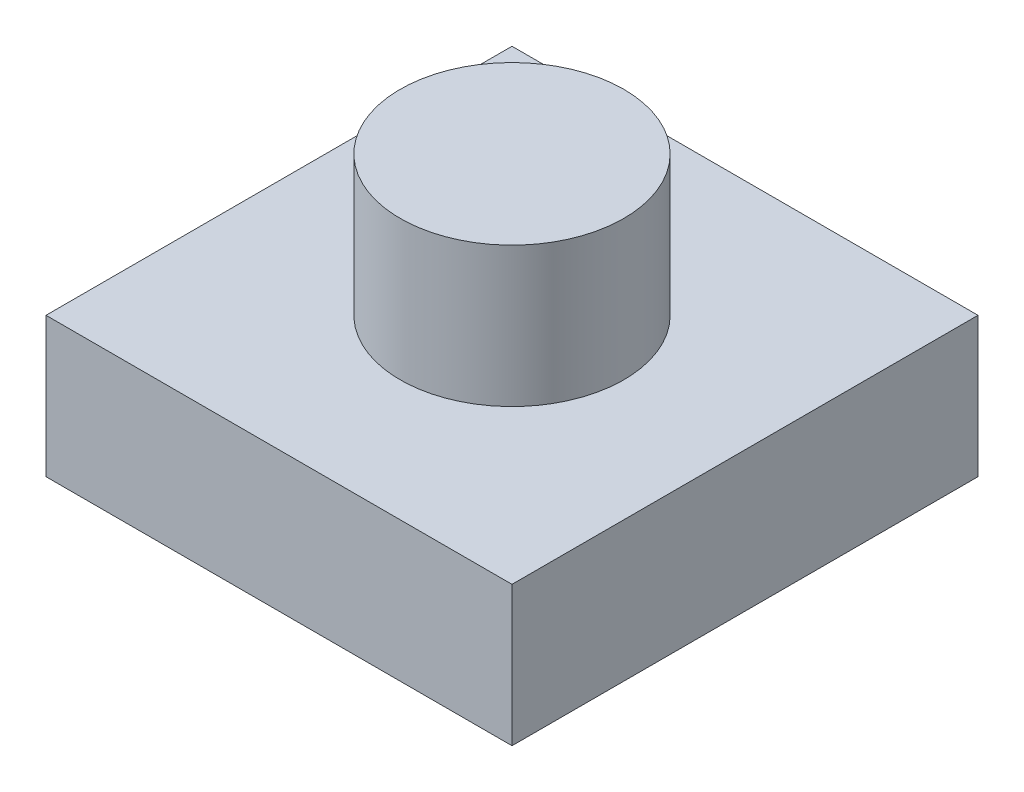
SolidWorks part; units mm, degrees
ref_plane "Front Plane" through (0, 0, 0) normal (0, 0, 1) x (1, 0, 0)
ref_plane "Top Plane" through (0, 0, 0) normal (0, 1, 0) x (1, 0, 0)
ref_plane "Right Plane" through (0, 0, 0) normal (1, 0, 0) x (0, 0, -1)
sketch "Sketch1" plane through (0, 0, 0) normal (0, 1, 0) x (1, 0, 0)
  line L1 (-6.35, 6.35) -> (6.35, 6.35)
  line L2 (-6.35, 6.35) -> (-6.35, -6.35)
  line L3 (-6.35, -6.35) -> (6.35, -6.35)
  line L4 (6.35, 6.35) -> (6.35, -6.35)
  dimension "D1" = 12.7
  dimension "D2" = 12.7
extrude "Boss-Extrude1" add sketch "Sketch1" along normal blind 3.81
sketch "Sketch2" plane through (0, 3.81, 0) normal (0, 1, 0) x (1, 0, 0)
  line L0 (6.35, -6.35) -> (6.35, 6.35) construction
  line L1 (6.35, 6.35) -> (-6.35, 6.35) construction
  circle A0 centre (0, 0) radius 3.048
  dimension "D1" = 6.35
  dimension "D2" = 6.35
extrude "Boss-Extrude2" add sketch "Sketch2" along normal blind 3.81
